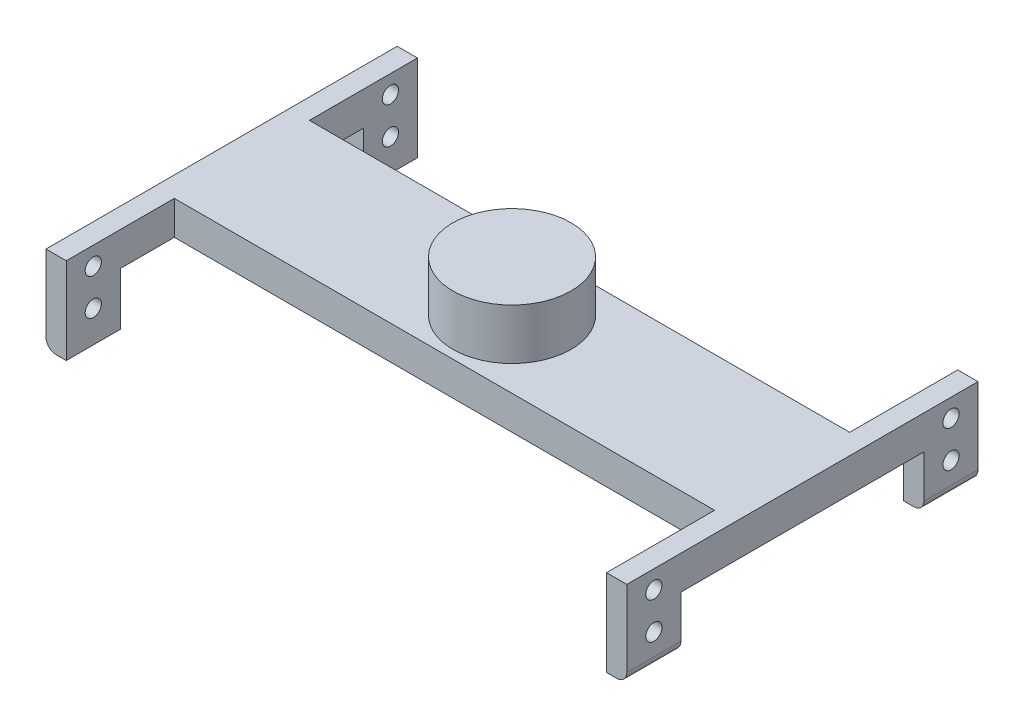
SolidWorks part; units mm, degrees
ref_plane "Front Plane" through (0, 0, 0) normal (0, 0, 1) x (1, 0, 0)
ref_plane "Top Plane" through (0, 0, 0) normal (0, 1, 0) x (1, 0, 0)
ref_plane "Right Plane" through (0, 0, 0) normal (1, 0, 0) x (0, 0, -1)
sketch "Sketch1" plane through (0, 0, 0) normal (0, 1, 0) x (1, 0, 0)
  line L1 (-40, -10) -> (40, -10)
  line L2 (-40, -10) -> (-40, 10)
  line L3 (-40, 10) -> (40, 10)
  line L4 (40, -10) -> (40, 10)
  line L5 (-40, -10) -> (40, 10) construction
  line L6 (-40, 10) -> (40, -10) construction
  point P1 (0, 0)
  dimension "D1" = 20
  dimension "D2" = 80
extrude "Boss-Extrude1" add sketch "Sketch1" along normal blind 2.5 and the other way blind 2.5
sketch "Sketch2" plane through (40, 0, 0) normal (1, 0, 0) x (0, 0, -1)
  line L0 (0, 2.5) -> (0, -2.5) construction
  line L1 (-10, -2.5) -> (10, -2.5) construction
  line L2 (-26, 2.5) -> (26, 2.5)
  line L3 (26, 2.5) -> (26, -10.3)
  line L4 (26, -10.3) -> (18, -10.3)
  line L5 (18, -10.3) -> (18, -2.5)
  line L6 (18, -2.5) -> (-18, -2.5)
  line L7 (-18, -10.3) -> (-18, -2.5)
  line L8 (-26, -10.3) -> (-18, -10.3)
  line L9 (-26, 2.5) -> (-26, -10.3)
  point P0 (-0.3258, -2.5)
  point P6 (0, 0)
  dimension "D1" = 52
  dimension "D2" = 8
  dimension "D3" = 12.8
extrude "Boss-Extrude2" add sketch "Sketch2" along normal blind 3
mirror "Mirror2" about plane through (0, 0, 0) normal (1, 0, 0) of "Boss-Extrude2"
fillet "Fillet1" radius 1.5 4 edges at (43, -10.3, 22) (43, -10.3, -22) (-43, -10.3, 22) (-43, -10.3, -22)
sketch "Sketch3" plane through (43, 0, 0) normal (1, 0, 0) x (0, 0, -1)
  circle A0 centre (22, -0.2) radius 1.2 construction
  circle A1 centre (-22, -0.2) radius 1.2 construction
  circle A2 centre (-22, -5.6) radius 1.2 construction
  circle A3 centre (22, -5.6) radius 1.2 construction
  circle A4 centre (22, -0.2) radius 1.2
  circle A5 centre (-22, -0.2) radius 1.2
  circle A6 centre (-22, -5.6) radius 1.2
  circle A7 centre (22, -5.6) radius 1.2
extrude "Cut-Extrude1" cut sketch "Sketch3" against normal through all both and the other way through all
sketch "Sketch4" plane through (0, 0, 0) normal (0, 1, 0) x (1, 0, 0)
  circle A0 centre (0, 0) radius 8.75
  dimension "D1" = 17.5
extrude "Boss-Extrude3" add sketch "Sketch4" along normal blind 7.5 from surface starting at face at (0, 2.5, 0)
